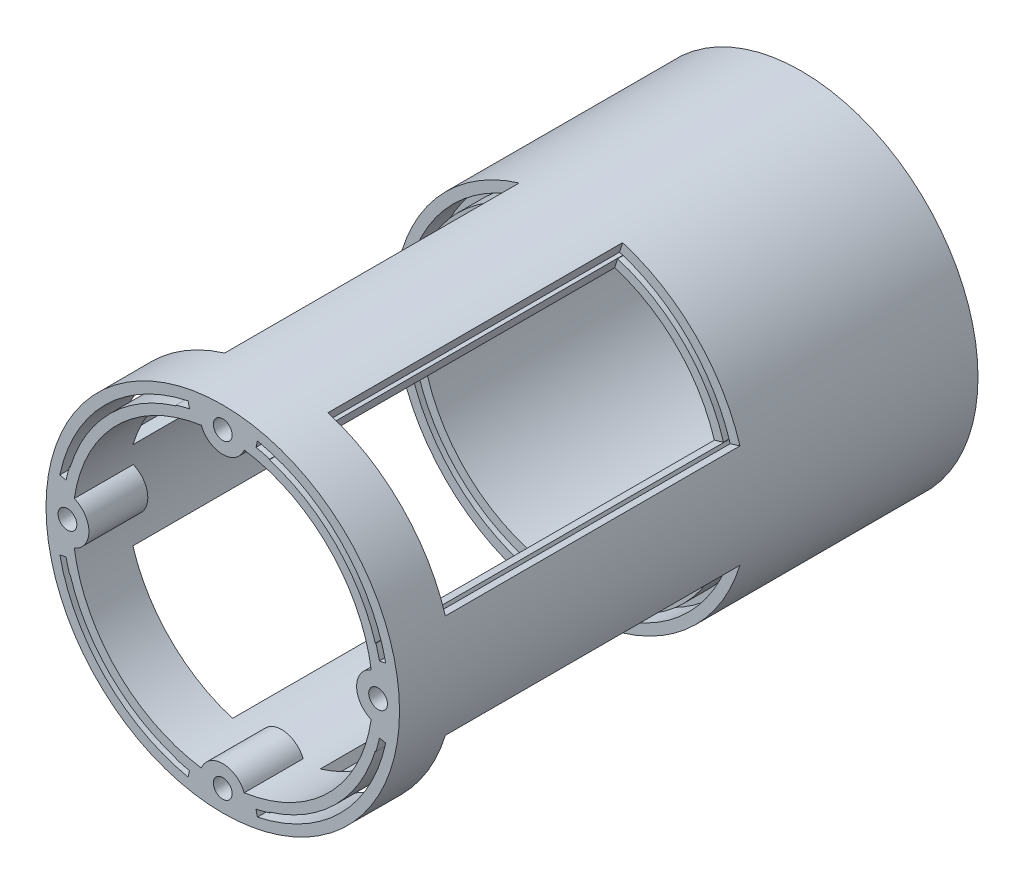
SolidWorks part; units mm, degrees
material "ABS"
ref_plane "Alzado" through (0, 0, 0) normal (0, 0, 1) x (1, 0, 0)
ref_plane "Planta" through (0, 0, 0) normal (0, 1, 0) x (1, 0, 0)
ref_plane "Vista lateral" through (0, 0, 0) normal (1, 0, 0) x (0, 0, -1)
sketch "Croquis1" plane through (0, 0, 0) normal (0, 0, 1) x (1, 0, 0)
  circle A0 centre (0, 0) radius 33
  circle A1 centre (0, 0) radius 28
  dimension "D1" = 66
  dimension "D2" = 5
extrude "Boss-Extrude1" add sketch "Croquis1" along normal blind 108
sketch "Croquis2" plane through (0, 0, 108) normal (0, 0, 1) x (1, 0, 0)
  line L0 (0, 0) -> (-6.4661, -30.4204) construction
  line L1 (0, 0) -> (-30.4204, -6.4661) construction
  line L2 (0, 0) -> (0, -30.5) construction
  line L3 (0, 0) -> (-30.5, 0) construction
  line L4 (-30.4204, -6.4661) -> (-29.2466, -6.2166)
  line L5 (-6.4661, -30.4204) -> (-6.2166, -29.2466)
  line L6 (-30.4204, 6.4661) -> (-29.2466, 6.2166)
  line L7 (-6.4661, 30.4204) -> (-6.2166, 29.2466)
  line L8 (6.4661, 30.4204) -> (6.2166, 29.2466)
  line L9 (30.4204, 6.4661) -> (29.2466, 6.2166)
  line L10 (30.4204, -6.4661) -> (29.2466, -6.2166)
  line L11 (6.4661, -30.4204) -> (6.2166, -29.2466)
  circle A0 centre (0, 0) radius 29.9 construction
  circle A1 centre (0, 0) radius 31.1 construction
  circle A2 centre (0, 0) radius 33 construction
  circle A3 centre (0, 0) radius 30.5 construction
  arc A4 (-6.4661, -30.4204) -> (-30.4204, -6.4661) centre (0, 0) cw
  arc A5 (-6.2166, -29.2466) -> (-29.2466, -6.2166) centre (0, 0) cw
  arc A6 (-30.4204, 6.4661) -> (-6.4661, 30.4204) centre (0, 0) cw
  arc A7 (-29.2466, 6.2166) -> (-6.2166, 29.2466) centre (0, 0) cw
  arc A8 (6.4661, 30.4204) -> (30.4204, 6.4661) centre (0, 0) cw
  arc A9 (6.2166, 29.2466) -> (29.2466, 6.2166) centre (0, 0) cw
  arc A10 (30.4204, -6.4661) -> (6.4661, -30.4204) centre (0, 0) cw
  arc A11 (29.2466, -6.2166) -> (6.2166, -29.2466) centre (0, 0) cw
  circle A12 centre (0, 0) radius 28 construction
  point P4 (-6.3413, -29.8335)
  point P32 (0, 0)
  dimension "D3" = 12
  dimension "D4" = 12
  dimension "D1" = 1.2
  dimension "D2" = 5
  dimension "D6" = 2.5
  dimension "D5" = 4
extrude "Cortar-Extruir1" cut sketch "Croquis2" against normal blind 70
ref_axis "Eje1" through (0, 0, 108) along (0, 0, -1)
ref_plane "Plano2" through (0, 0, 0) normal (0.9563, -0.2924, 0) x (0, 0, -1)
sketch "Croquis4" plane through (0, 0, 0) normal (0.9563, -0.2924, 0) x (0, 0, -1)
  line L0 (-98, 33) -> (-98, 30.9839)
  line L1 (0, 33) -> (-108, 33) construction
  line L2 (-98, 27.7679) -> (-43, 27.7679)
  line L3 (-43, 27.7679) -> (-43, 29.7839)
  line L4 (-43, 33) -> (-98, 33)
  line L5 (-97, 29) -> (-42, 29) construction
  line L6 (-108, 33) -> (-108, -33) construction
  line L7 (-108, 30.9839) -> (-98, 30.9839)
  line L8 (-38, 30.9839) -> (-38, 29.7839)
  line L9 (-38, 29.7839) -> (-43, 29.7839)
  line L10 (-108, 29.7839) -> (-108, 30.9839)
  line L11 (-98, 29.7839) -> (-108, 29.7839)
  line L12 (-98, 29.7839) -> (-98, 27.7679)
  line L13 (-43, 30.9839) -> (-38, 30.9839)
  line L14 (-43, 30.9839) -> (-43, 33)
  line L15 (-108, 30.9817) -> (-108, 29.7862) construction
  point P20 (-108, 30.3839)
  point P21 (-108, 30.3839)
  dimension "D2" = 65
  dimension "D3" = 1.2
  dimension "D5" = 5
  dimension "D6" = 10
revolve "Cortar-Revolución2" cut sketch "Croquis4" angle 56 about axis through (0, 0, 108) along (0, 0, -1)
pattern_circular "MatrizC2" count 4 over 360 about axis through (0, 0, 108) along (0, 0, -1) of "Cortar-Revolución2"
sketch "Sketch8" plane through (0, 0, 0) normal (0, 0, -1) x (-1, 0, 0)
  arc A0 (-4, -27.7128) -> (4, -27.7128) centre (0, 0) ccw
  circle A1 centre (0, 0) radius 28 construction
  arc A2 (-4, -27.7128) -> (4, -27.7128) centre (0, -29.2908) cw
  arc A3 (-27.7128, 4) -> (-27.7128, -4) centre (0, 0) ccw
  arc A4 (-27.7128, 4) -> (-27.7128, -4) centre (-29.2908, 0) cw
  arc A5 (4, 27.7128) -> (-4, 27.7128) centre (0, 0) ccw
  arc A6 (4, 27.7128) -> (-4, 27.7128) centre (0, 29.2908) cw
  arc A7 (27.7128, -4) -> (27.7128, 4) centre (0, 0) ccw
  arc A8 (27.7128, -4) -> (27.7128, 4) centre (29.2908, 0) cw
  point P8 (0, -24.9908)
  point P20 (0, 0)
  dimension "D1" = 4.3
  dimension "D2" = 8
  dimension "D3" = 4
extrude "Boss-Extrude4" add sketch "Sketch8" against normal blind 11
sketch "Sketch9" plane through (0, 0, 0) normal (0, 0, -1) x (-1, 0, 0)
  circle A0 centre (0, -29) radius 1.75
  circle A1 centre (0, 0) radius 29 construction
  circle A2 centre (0, 0) radius 33 construction
  circle A3 centre (-29, 0) radius 1.75
  circle A4 centre (0, 29) radius 1.75
  circle A5 centre (29, 0) radius 1.75
  point P16 (0, 0)
  dimension "D1" = 4
  dimension "D2" = 3.5
  dimension "D3" = 4
extrude "Cut-Extrude3" cut sketch "Sketch9" against normal blind 10
ref_plane "Mid plane" through (0, 0, 54) normal (0, 0, 1) x (1, 0, 0)
mirror "Mirror1" about plane through (0, 0, 54) normal (0, 0, 1) of "Cut-Extrude3", "Boss-Extrude4"
equation "\"D6@Croquis2\"=\"D2@Croquis2\"/2"
